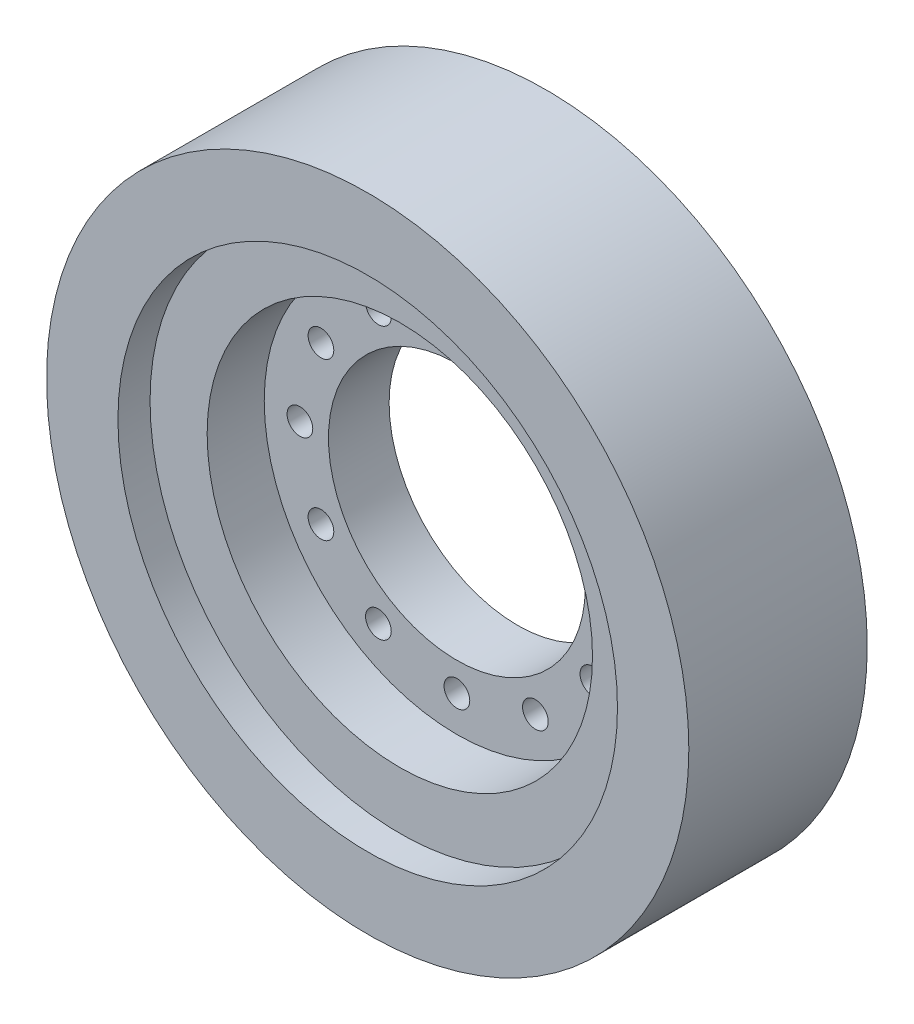
SolidWorks part; units mm, degrees
ref_plane "前视基准面" through (0, 0, 0) normal (0, 0, 1) x (1, 0, 0)
ref_plane "上视基准面" through (0, 0, 0) normal (0, 1, 0) x (1, 0, 0)
ref_plane "右视基准面" through (0, 0, 0) normal (1, 0, 0) x (0, 0, -1)
sketch "草图1" plane through (0, 0, 0) normal (0, 0, 1) x (1, 0, 0)
  circle A0 centre (0, 0) radius 45
  dimension "D1" = 90
extrude "凸台-拉伸2" add sketch "草图1" along normal blind 25 contours A0
sketch "草图2" plane through (0, 0, 25) normal (0, 0, 1) x (1, 0, 0)
  circle A0 centre (0, 0) radius 35
  dimension "D1" = 70
extrude "切除-拉伸1" cut sketch "草图2" against normal blind 4.5
sketch "草图3" plane through (0, 0, 20.5) normal (0, 0, 1) x (1, 0, 0)
  circle A0 centre (0, 0) radius 27
  dimension "D1" = 54
extrude "切除-拉伸2" cut sketch "草图3" against normal blind 8
sketch "草图4" plane through (0, 0, 12.5) normal (0, 0, 1) x (1, 0, 0)
  circle A0 centre (0, 0) radius 18
  dimension "D1" = 36
extrude "切除-拉伸3" cut sketch "草图4" against normal blind 8.5
sketch "草图10" plane through (0, 0, 0) normal (0, 0, -1) x (-1, 0, 0)
  circle A0 centre (0, 0) radius 42.5
  dimension "D1" = 85
extrude "切除-拉伸5" cut sketch "草图10" against normal blind 4 contours A0
ref_axis "基准轴1" through (0, 0, 25) along (0, 0, -1)
hole_wizard "打孔尺寸(%根据)内六角圆柱头螺钉的类型2" positions "草图12" profile "草图11" counterbore size "M3" standard "GB" end condition through all
sketch "草图12" plane through (0, 0, 4) normal (0, 0, -1) x (-1, 0, 0)
  line L0 (0, 0) -> (0, 48.0273) construction
  circle A0 centre (0, 0) radius 22 construction
  point P0 (0, 22)
  dimension "D1" = 44
sketch "草图11" plane through (0, 22, 4) normal (1, 0, 0) x (0, 1, 0)
  line L0 (0, 0) -> (0, 21)
  line L1 (0, 21) -> (1.8, 21)
  line L3 (1.8, 21) -> (1.8, 3.4)
  line L4 (1.8, 3.4) -> (3, 3.4)
  line L5 (3, 3.4) -> (3, 0)
  line L7 (3, 0) -> (0, 0)
  line L11 (0, -6.35) -> (0, 107.95) construction
  dimension "通孔孔直径" = 3.6
  dimension "通孔孔深度" = 21
  dimension "柱形沉头孔直径" = 6
  dimension "柱形沉头孔深度" = 3.4
pattern_circular "阵列(圆周)2" count 12 over 360 about axis through (0, 0, 25) along (0, 0, -1) of "打孔尺寸(%根据)内六角圆柱头螺钉的类型2"
hole_wizard "M3 螺纹孔1" positions "草图18" profile "草图17" tap size "M3" standard "GB"
sketch "草图18" plane through (0, 0, 4) normal (0, 0, -1) x (-1, 0, 0)
  line L0 (0, 0) -> (0, 47.142) construction
  circle A0 centre (0, 0) radius 37.5 construction
  point P0 (0, 37.5)
  dimension "D1" = 75
sketch "草图17" plane through (0, 37.5, 4) normal (1, 0, 0) x (0, 1, 0)
  line L0 (0, 0) -> (0, 7.2511)
  line L1 (0, 7.2511) -> (1.25, 6.5)
  line L2 (1.25, 6.5) -> (1.25, 0)
  line L5 (1.25, 0) -> (0, 0)
  line L10 (0, 7.2511) -> (-1.25, 6.5) construction
  line L11 (0, -6.35) -> (0, 107.95) construction
  dimension "螺纹孔钻头直径" = 2.5
  dimension "螺纹孔钻头深度" = 6.5
  dimension "导头角度" = 118
cosmetic thread "孔螺蚊线1" parameters "D1"=5, "D2"=3
pattern_circular "阵列(圆周)3" count 8 over 360 about axis through (0, 0, 25) along (0, 0, -1) of "M3 螺纹孔1"
